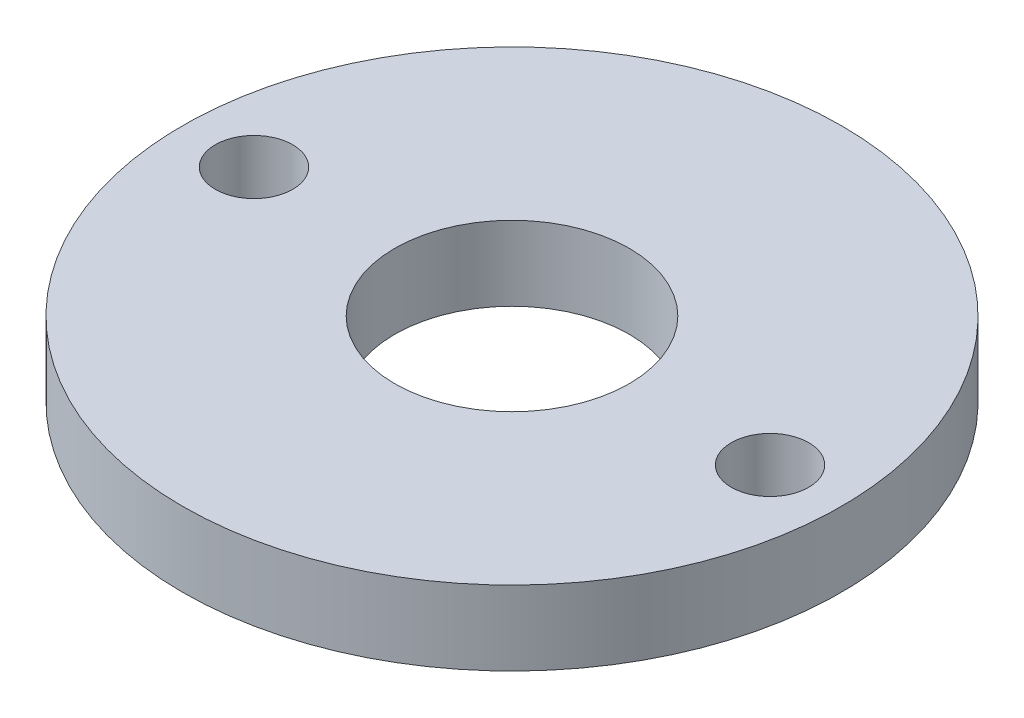
SolidWorks part; units mm, degrees
ref_plane "Front Plane" through (0, 0, 0) normal (0, 0, 1) x (1, 0, 0)
ref_plane "Top Plane" through (0, 0, 0) normal (0, 1, 0) x (1, 0, 0)
ref_plane "Right Plane" through (0, 0, 0) normal (1, 0, 0) x (0, 0, -1)
sketch "Sketch1" plane through (0, 0, 0) normal (0, 1, 0) x (1, 0, 0)
  line L0 (11, 0) -> (-11, 0) construction
  circle A0 centre (0, 0) radius 14.05
  circle A1 centre (0, 0) radius 5
  circle A2 centre (11, 0) radius 1.65
  circle A3 centre (-11, 0) radius 1.65
  point P8 (9.4686, 0)
  point P11 (0, 0)
  dimension "D1" = 28.1
  dimension "D2" = 10
  dimension "D4" = 3.3
  dimension "D3" = 22
extrude "Boss-Extrude1" add sketch "Sketch1" along normal blind 3.175
